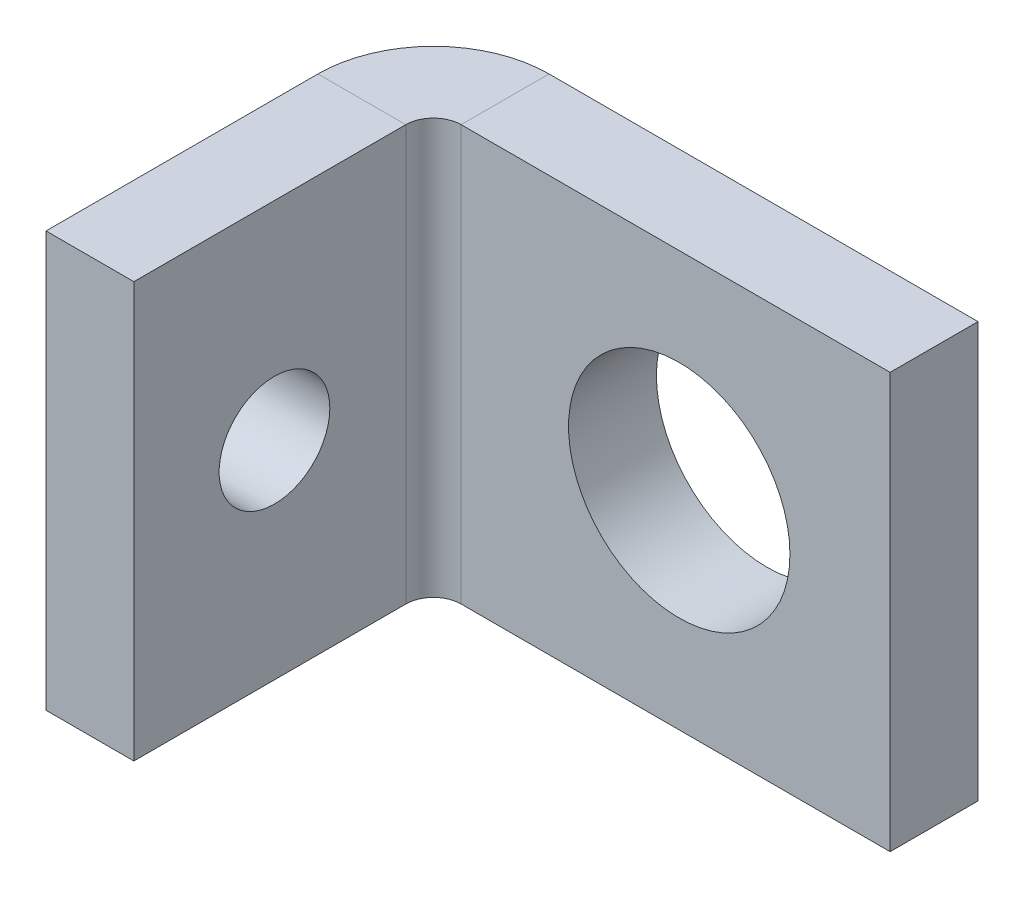
SolidWorks part; units mm, degrees
note: The reader was unsure of these and kept them because the rebuilt part matched: flange length of "Edge-Flange1".
material "3003-H14"
ref_plane "X-Y Datum" through (0, 0, 0) normal (0, 0, 1) x (1, 0, 0)
ref_plane "X-Z Datum" through (0, 0, 0) normal (0, 1, 0) x (1, 0, 0)
ref_plane "Y-Z Datum" through (0, 0, 0) normal (1, 0, 0) x (0, 0, -1)
sketch "Sketch1" plane through (0, 0, 0) normal (0, 0, 1) x (1, 0, 0)
  line L1 (-8.25, -7.5) -> (8.25, -7.5)
  line L2 (-8.25, -7.5) -> (-8.25, 7.5)
  line L3 (-8.25, 7.5) -> (8.25, 7.5)
  line L4 (8.25, -7.5) -> (8.25, 7.5)
  line L5 (-8.25, -7.5) -> (8.25, 7.5) construction
  line L6 (-8.25, 7.5) -> (8.25, -7.5) construction
  point P0 (0, 0)
  dimension "D1" = 15
  dimension "D2" = 16.5
base flange "Base-Flange1" sketch "Sketch1" thickness 3.175 reverse thickness direction yes parameters "D1"=10
edge flange "Edge-Flange1" sketch "Sketch8" flange angle 90 flange length 14 flange position material outside bend radius 1 thickness 3.175 relief rectangular parameters "D6"=10
sketch "Sketch8" plane through (-8.25, 0, 3.175) normal (1, 0, 0) x (0, 1, 0)
  line L2 (-7.5, 0) -> (-7.5, 10.825)
  line L3 (-7.5, 10.825) -> (7.5, 10.825)
  line L4 (7.5, 10.825) -> (7.5, 0)
  line L5 (7.5, 0) -> (-7.5, 0) construction
  line L6 (7.5, 0) -> (-7.5, 0)
bend "EdgeBend1" bend radius 1 bend angle 90 parameters "D5"=1
sketch "Sketch9" plane through (0, 0, 3.175) normal (0, 0, 1) x (1, 0, 0)
  line L0 (8.25, -7.5) -> (8.25, 7.5) construction
  line L2 (-7.25, -7.5) -> (8.25, -7.5) construction
  circle A0 centre (0.63, 0) radius 4
  dimension "D1" = 8
  dimension "D2" = 7.62
  dimension "D3" = 7.5
extrude "Cut-Extrude1" cut sketch "Sketch9" against normal blind 10 normal cut yes
sketch "Sketch10" plane through (-8.25, 0, 0) normal (1, 0, 0) x (0, 0, -1)
  line L0 (-14, 7.5) -> (-14, -7.5) construction
  line L2 (-4.175, 7.5) -> (-14, 7.5) construction
  circle A0 centre (-8.92, 0) radius 2
  dimension "D1" = 4
  dimension "D2" = 5.08
  dimension "D3" = 7.5
extrude "Cut-Extrude2" cut sketch "Sketch10" against normal blind 10 normal cut yes
sketch "Bend-Lines1" [suppressed] plane through (0, 0, 0) normal (0, 1, 0) x (1, 0, 0)
sketch "Bounding-Box1" [suppressed] plane through (0, 0, 0) normal (0, 1, 0) x (1, 0, 0)
sheet metal parameters "Sheet-Metal1" thickness 3.175 parameters "D1"=10
flat pattern "Flat-Pattern1" [suppressed]
sketch "Bend-Lines2" plane through (0, 0, 0) normal (0, 1, 0) x (1, 0, 0)
sketch3d "Bounding-Box2" [suppressed]
  line L0 (-8.25, -7.5, 0) -> (8.25, -7.5, 0) construction
  line L1 (-8.25, 7.5, 0) -> (8.25, 7.5, 0) construction
  line L2 (-8.25, -7.5, 0) -> (-8.25, 7.5, 0) construction
  line L3 (8.25, -7.5, 0) -> (8.25, 7.5, 0) construction
sheet metal parameters "Sheet-Metal2" thickness 3.175 parameters "D1"=10
flat pattern "Flat-Pattern1"
sketch "Bend-Lines2" plane through (0, 0, 0) normal (0, 0, -1) x (-1, 0, 0)
  line L0 (9.2822, -7.5) -> (9.2822, 7.5) construction
  line L1 (9.2822, -7.5) -> (9.2822, 7.5) construction
sketch3d "Bounding-Box2" [suppressed]
  line L0 (27.1394, -7.5, 0) -> (-8.25, -7.5, 0) construction
  line L1 (27.1394, 7.5, 0) -> (-8.25, 7.5, 0) construction
  line L2 (27.1394, -7.5, 0) -> (27.1394, 7.5, 0) construction
  line L3 (-8.25, -7.5, 0) -> (-8.25, 7.5, 0) construction
bend of the flat pattern "Flatten-<EdgeBend1>1"
sheet metal parameters "Sheet-Metal3" thickness 3.175 parameters "D1"=10
flat pattern "Flat-Pattern1"
sketch "Bend-Lines2" plane through (0, 0, 0) normal (0, 0, -1) x (-1, 0, 0)
  line L0 (9.2822, -7.5) -> (9.2822, 7.5) construction
  line L1 (9.2822, -7.5) -> (9.2822, 7.5) construction
sketch3d "Bounding-Box2" [suppressed]
  line L0 (27.1394, -7.5, 0) -> (-8.25, -7.5, 0) construction
  line L1 (27.1394, 7.5, 0) -> (-8.25, 7.5, 0) construction
  line L2 (27.1394, -7.5, 0) -> (27.1394, 7.5, 0) construction
  line L3 (-8.25, -7.5, 0) -> (-8.25, 7.5, 0) construction
bend of the flat pattern "Flatten-<EdgeBend1>1"
sheet metal parameters "Sheet-Metal4" thickness 3.175 parameters "D1"=10
flat pattern "Flat-Pattern1"
sketch "Bend-Lines2" plane through (0, 0, 0) normal (0, 0, -1) x (-1, 0, 0)
  line L0 (9.2822, -7.5) -> (9.2822, 7.5) construction
  line L1 (9.2822, -7.5) -> (9.2822, 7.5) construction
sketch3d "Bounding-Box2" [suppressed]
  line L0 (21.1394, -7.5, 0) -> (-8.25, -7.5, 0) construction
  line L1 (21.1394, 7.5, 0) -> (-8.25, 7.5, 0) construction
  line L2 (21.1394, -7.5, 0) -> (21.1394, 7.5, 0) construction
  line L3 (-8.25, -7.5, 0) -> (-8.25, 7.5, 0) construction
bend of the flat pattern "Flatten-<EdgeBend1>1"
